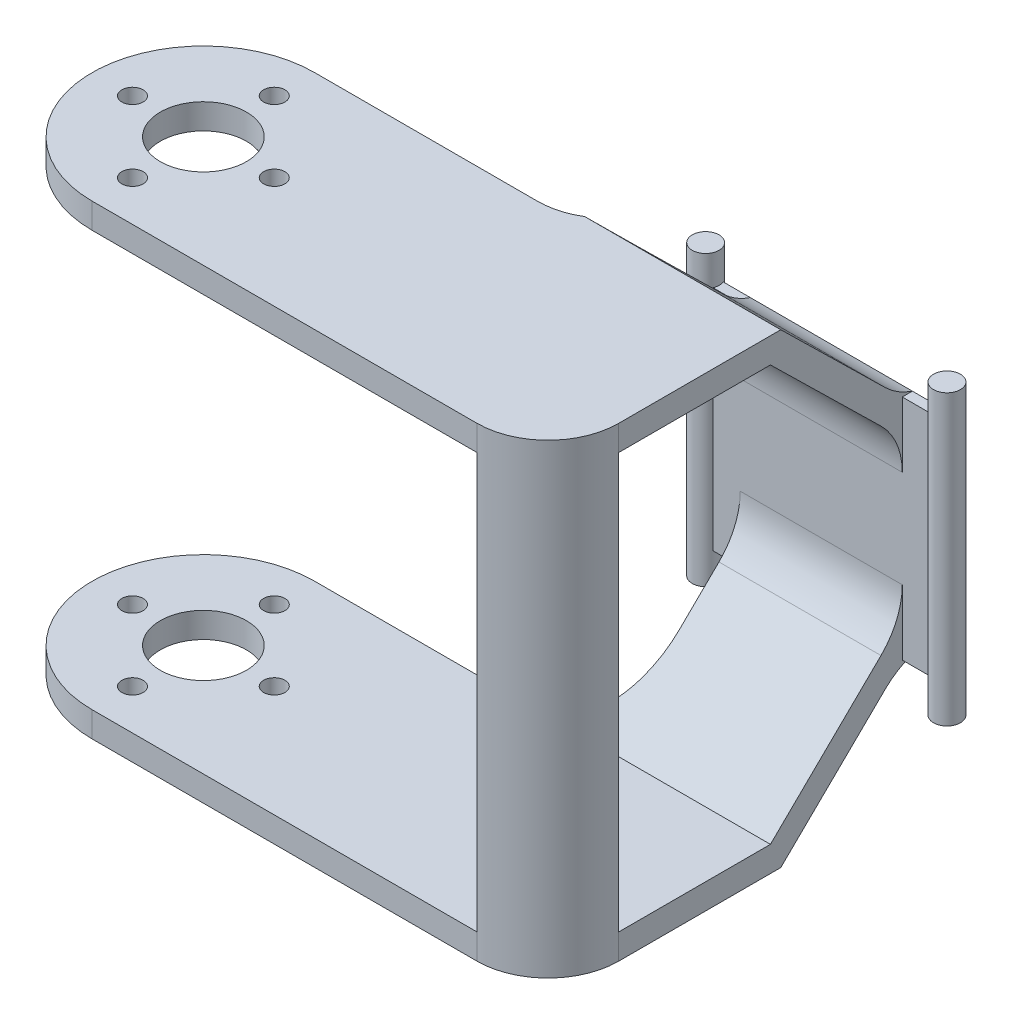
SolidWorks part; units mm, degrees
ref_plane "Front Plane" through (0, 0, 0) normal (0, 0, 1) x (1, 0, 0)
ref_plane "Top Plane" through (0, 0, 0) normal (0, 1, 0) x (1, 0, 0)
ref_plane "Right Plane" through (0, 0, 0) normal (1, 0, 0) x (0, 0, -1)
sketch "Sketch1" plane through (0, 0, 0) normal (0, 1, 0) x (1, 0, 0)
  line L1 (11.915, 0.5) -> (-11.915, 0.5)
  line L2 (11.915, 0.5) -> (11.915, -0.5)
  line L3 (11.915, -0.5) -> (-11.915, -0.5)
  line L4 (-11.915, 0.5) -> (-11.915, -0.5)
  line L5 (11.915, 0.5) -> (-11.915, -0.5) construction
  line L6 (11.915, -0.5) -> (-11.915, 0.5) construction
  point P0 (0, 0)
  dimension "D1" = 23.83
  dimension "D3" = 1
extrude "Boss-Extrude1" add sketch "Sketch1" along normal blind 22.5
ref_plane "Plane1" through (0, 11.25, 0) normal (0, 1, 0) x (1, 0, 0)
sketch "Sketch2" plane through (0, 11.25, 0) normal (0, 1, 0) x (1, 0, 0)
  line L0 (11.915, -0.5) -> (11.915, 0.5) construction
  line L1 (-11.915, 0.5) -> (-11.915, -0.5) construction
  line L2 (11.915, -0.5) -> (11.915, 0.5) construction
  line L3 (-11.915, 0.5) -> (-11.915, -0.5) construction
  circle A0 centre (-11.915, 0) radius 1.325
  circle A1 centre (11.915, 0) radius 1.325
  dimension "D1" = 2.65
extrude "Boss-Extrude2" add sketch "Sketch2" along normal mid plane 28.5
sketch "Sketch3" plane through (0, 22.5, 0) normal (0, 1, 0) x (1, 0, 0)
  line L0 (-10.688, -0.5) -> (10.688, -0.5) construction
  line L1 (-7.5, -0.5) -> (7.5, -0.5)
  line L2 (-7.5, -0.5) -> (-7.5, -26.5)
  line L3 (-7.5, -26.5) -> (7.5, -26.5)
  line L4 (7.5, -0.5) -> (7.5, -26.5)
  line L5 (0, -1000) -> (0, 49000) construction
  line L6 (-7.5, -26.5) -> (-32.5, -26.5)
  line L7 (-7.5, -26.5) -> (-7.5, -3.5)
  line L8 (-7.5, -3.5) -> (-32.5, -3.5)
  line L9 (-32.5, -26.5) -> (-32.5, -3.5)
  line L11 (-4.5, -3.5) -> (4.5, -3.5)
  line L12 (4.5, -3.5) -> (4.5, -23.5)
  line L13 (-4.5, -23.5) -> (4.5, -23.5)
  line L14 (-10.5, -23.5) -> (-29.5, -23.5)
  line L16 (-10.5, -6.5) -> (-29.5, -6.5)
  line L18 (-29.5, -23.5) -> (-29.5, -6.5) construction
  line L19 (-10.5, -23.5) -> (-10.5, -6.5) construction
  line L20 (-4.5, -3.5) -> (-4.5, -23.5) construction
  line L21 (-4.5, -3.5) -> (-4.5, -6.5)
  line L22 (-4.5, -6.5) -> (-10.5, -6.5)
  line L23 (-4.5, -23.5) -> (-10.5, -23.5)
  line L24 (-18.5, -6.5) -> (-18.5, -23.5)
  circle A0 centre (-32.5, -15) radius 11.5
  circle A1 centre (-32.5, -15) radius 4.25
  circle A2 centre (-32.5, -15) radius 7 construction
  circle A3 centre (-32.5, -8) radius 1.05
  circle A4 centre (-25.5, -15) radius 1.05
  circle A5 centre (-32.5, -22) radius 1.05
  circle A6 centre (-39.5, -15) radius 1.05
  point P10 (0, -0.5)
  line M14 (-10.688, -0.5) -> (10.688, -0.5)
  dimension "D5" = 8.5
  dimension "D6" = 14
  dimension "D7" = 2.1
  dimension "D1" = 15
  dimension "D2" = 26
  dimension "D3" = 23
  dimension "D4" = 25
  dimension "D9" = 14
  dimension "D8" = 3
extrude "Boss-Extrude3" [suppressed] add sketch "Sketch3" against normal up to surface (18.5 mm away) contours L4 L2 L3 M14 | A0 L6 L2 L8 | A5 L9 A0 A3 A1 A4 | A5 L9 A1 A3 A0 A6 | A0 L16 L22 L2 L8 | A0 L6 L2 L23 L14
sketch "Sketch4" plane through (0, 0, 0) normal (1, 0, 0) x (0, 0, -1)
  line L0 (-0.5, 22.5) -> (-12.5, 34.25)
  line L1 (-12.5, 34.25) -> (-35.5, 34.25)
  line L2 (-35.5, 34.25) -> (-35.5, 31.75)
  line L3 (-35.5, 31.75) -> (-13.5202, 31.75)
  line L4 (-13.5202, 31.75) -> (-0.5, 19.0011)
  line L5 (-0.5, 22.5) -> (-0.5, 0) construction
  line L6 (-0.5, 22.5) -> (-0.5, 0)
  line L7 (-0.5, 0) -> (-12.5, -11.75)
  line L8 (-12.5, -11.75) -> (-35.5, -11.75)
  line L9 (-35.5, -11.75) -> (-35.5, -9.25)
  line L10 (-35.5, -9.25) -> (-13.5202, -9.25)
  line L11 (-13.5202, -9.25) -> (-0.5, 3.4989)
  line L12 (-1000.5, 11.25) -> (48999.5, 11.25) construction
  line L13 (-35.5, 31.75) -> (-35.5, -9.25) construction
  point P3 (-35.5, 11.25)
  point P20 (-0.5, 11.25)
  dimension "D1" = 2.5
  dimension "D2" = 41
  dimension "D3" = 23
  dimension "D4" = 2.5
  dimension "D5" = 35
  dimension "D6" = 2.5
extrude "Boss-Extrude4" add sketch "Sketch4" along normal mid plane 16 contours L6 L0 L1 L2 L3 L4 | L11 L10 L9 L8 L7 L6
sketch "Sketch5" plane through (-8, 0, 0) normal (-1, 0, 0) x (0, 0, 1)
  line L1 (35.5, 34.25) -> (13.5202, 34.25)
  line L2 (35.5, 34.25) -> (35.5, 31.75)
  line L3 (35.5, 31.75) -> (13.5202, 31.75)
  line L4 (13.5202, 34.25) -> (13.5202, 31.75)
  line L5 (35.5, -11.75) -> (13.5202, -11.75)
  line L6 (35.5, -11.75) -> (35.5, -9.25)
  line L7 (35.5, -9.25) -> (13.5202, -9.25)
  line L8 (13.5202, -11.75) -> (13.5202, -9.25)
extrude "Boss-Extrude5" add sketch "Sketch5" along normal blind 40
sketch "Sketch6" plane through (0, 34.25, 0) normal (0, 1, 0) x (1, 0, 0)
  line L0 (-37.0101, -13.5202) -> (-37.0101, -35.5) construction
  line L1 (-48, -13.5202) -> (-8, -13.5202) construction
  line L2 (8, -35.5) -> (-48, -35.5) construction
  line L3 (-48, -24.5101) -> (8, -24.5101) construction
  line L4 (-48, -35.5) -> (-48, -13.5202) construction
  line L5 (8, -12.5) -> (8, -35.5) construction
  line L6 (-37.0101, -13.5202) -> (-48, -13.5202)
  line L7 (-48, -13.5202) -> (-48, -35.5)
  line L8 (-48, -35.5) -> (-37.0101, -35.5)
  circle A0 centre (-37.0101, -24.5101) radius 10.9899
  circle A1 centre (-37.0101, -24.5101) radius 4.25
  circle A2 centre (-37.0101, -24.5101) radius 7 construction
  circle A3 centre (-37.0101, -17.5101) radius 1.05
  circle A4 centre (-30.0101, -24.5101) radius 1.05
  circle A5 centre (-37.0101, -31.5101) radius 1.05
  circle A6 centre (-44.0101, -24.5101) radius 1.05
  point P12 (-37.0101, -24.5101)
  line M9 (-8, -13.5202) -> (-48, -13.5202)
  line M10 (-48, -13.5202) -> (-48, -35.5)
  line M11 (-48, -35.5) -> (8, -35.5)
  dimension "D1" = 8.5
  dimension "D2" = 14
  dimension "D3" = 2.1
extrude "Cut-Extrude1" cut sketch "Sketch6" against normal through all contours A1 | A6 | A3 | A4 | A5 | A0 M9 M10 | A0 L7 M11
fillet "Fillet1" radius 7 4 edges at (-8, -10.5, 13.5202) (-8, 33, 13.5202) (8, -10.5, 35.5) (8, 33, 35.5)
fillet "Fillet2" radius 7 2 edges at (0, 3.4989, 0.5) (0, 19.0011, 0.5)
fillet "Fillet3" radius 7 2 edges at (0, 22.5, 0.5) (0, 0, 0.5)
sketch "Sketch8" plane through (0, -9.25, 0) normal (0, 1, 0) x (1, 0, 0)
  line L0 (-37.0101, -13.5202) -> (-15, -13.5202) construction
  line L1 (-37.0101, -13.5202) -> (-15, -13.5202)
  line L2 (8, -28.5) -> (5, -28.5)
  line L3 (1, -35.5) -> (1, -32.5)
  arc A0 (-15, -13.5202) -> (-8, -6.5202) centre (-15, -6.5202) ccw construction
  arc A1 (1, -35.5) -> (8, -28.5) centre (1, -28.5) ccw construction
  arc A2 (-15, -13.5202) -> (-8, -6.5202) centre (-15, -6.5202) ccw
  arc A3 (1, -35.5) -> (8, -28.5) centre (1, -28.5) ccw
  circle A4 centre (-1.5277, -25.9723) radius 7
  arc M10 (1, -35.5) -> (8, -28.5) centre (1, -28.5) ccw
  dimension "D1" = 3
extrude "Boss-Extrude6" add sketch "Sketch8" along normal up to surface (41 mm away) contours A4 L3 L2 M10 up to face at (-37.0101, 31.75, 28.7601)
equation "\"D4@Sketch4\"=\"D1@Sketch4\""
equation "\"D6@Sketch4\"=\"D1@Sketch4\""
